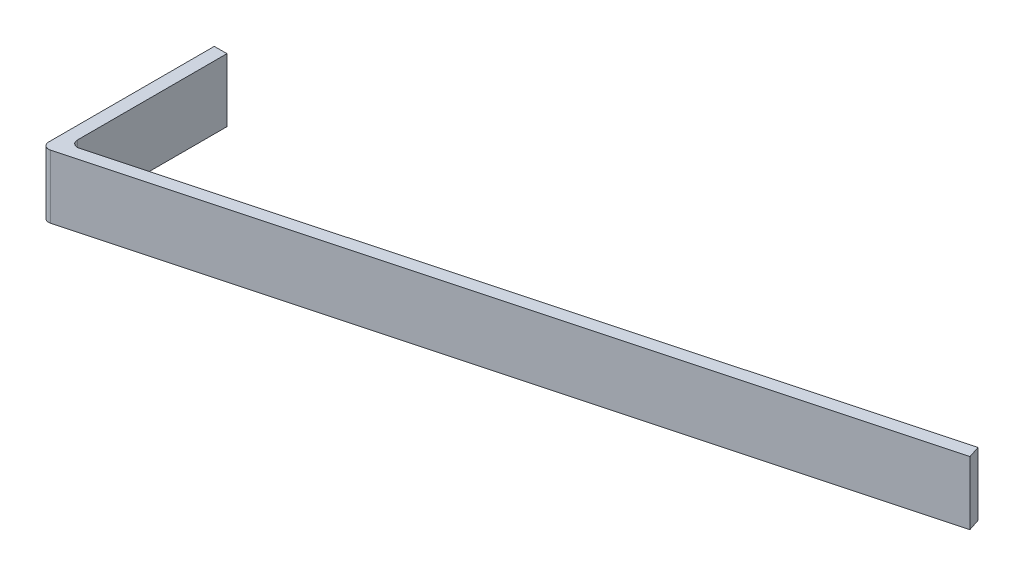
SolidWorks part; units mm, degrees
ref_plane "Front Plane" through (0, 0, 0) normal (0, 0, 1) x (1, 0, 0)
ref_plane "Top Plane" through (0, 0, 0) normal (0, 1, 0) x (1, 0, 0)
ref_plane "Right Plane" through (0, 0, 0) normal (1, 0, 0) x (0, 0, -1)
sketch "Sketch1" plane through (0, 0, 0) normal (0, 1, 0) x (1, 0, 0)
  line L0 (0, 0) -> (2, 0.5359)
  line L2 (0, 0) -> (0, 27.5)
  line L3 (0, 27.5) -> (2, 27.5)
  line L4 (2, 0.5359) -> (2, 27.5)
  dimension "D2" = 27.5
  dimension "D3" = 75
extrude "Boss-Extrude1" add sketch "Sketch1" along normal blind 10
sketch "Sketch3" plane through (0, 0, 0) normal (0, -1, 0) x (1, 0, 0)
  line L0 (0, 0) -> (115.9111, -31.0583)
  line L1 (0, 0) -> (0, -2)
  line L2 (0, -27.5) -> (0, 0) construction
  line L3 (0, -2) -> (115.2858, -32.958)
  line L4 (115.2858, -32.958) -> (115.9111, -31.0583)
  dimension "D1" = 75
  dimension "D2" = 2
  dimension "D3" = 2
extrude "Boss-Extrude2" add sketch "Sketch3" against normal blind 10
fillet "Fillet1" radius 1 2 edges at (0, 5, 0) (2, 5, -2.5371)
